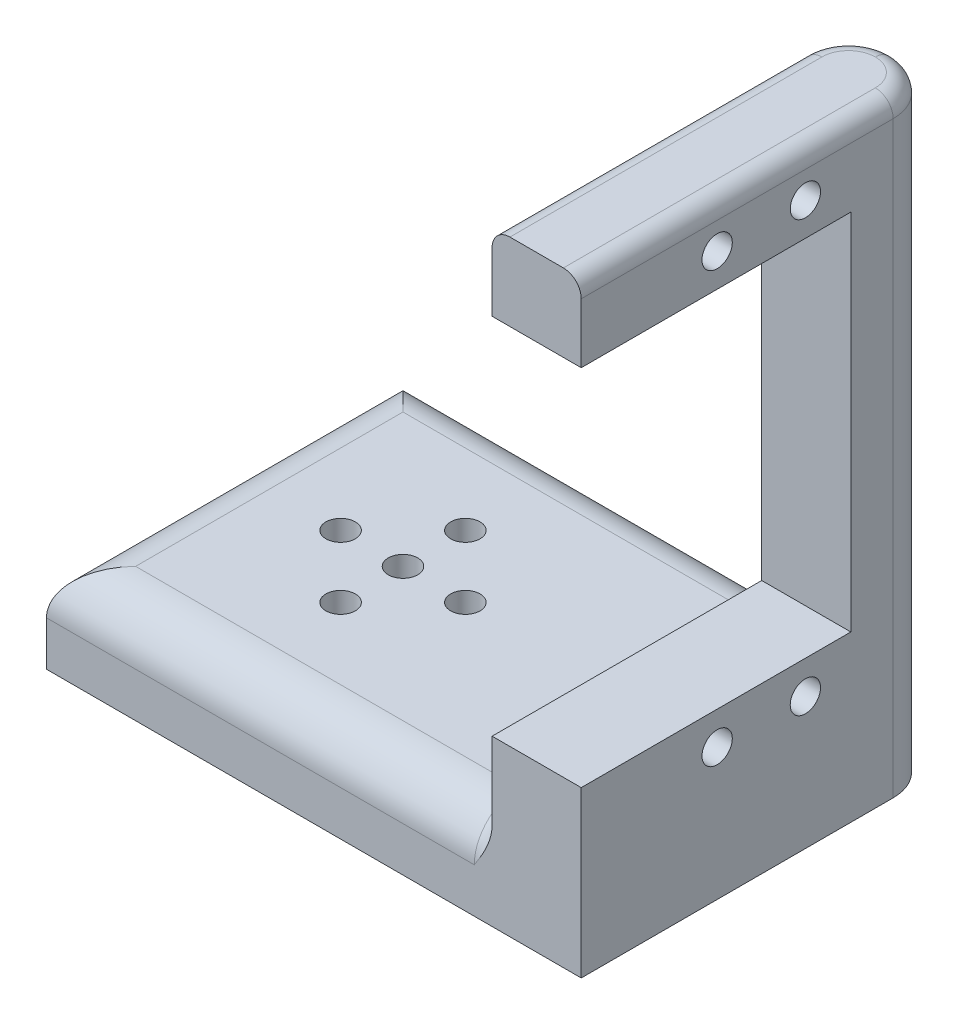
SolidWorks part; units mm, degrees
ref_plane "Front Plane" through (0, 0, 0) normal (0, 0, 1) x (1, 0, 0)
ref_plane "Top Plane" through (0, 0, 0) normal (0, 1, 0) x (1, 0, 0)
ref_plane "Right Plane" through (0, 0, 0) normal (1, 0, 0) x (0, 0, -1)
sketch "Sketch1" plane through (0, 0, 0) normal (0, 0, 1) x (1, 0, 0)
  line L0 (0, 0) -> (0, 68)
  line L1 (0, 68) -> (-10, 68)
  line L2 (-10, 68) -> (-10, 10)
  line L3 (-10, 10) -> (-60, 10)
  line L4 (-60, 10) -> (-60, 0)
  line L5 (-60, 0) -> (0, 0)
  dimension "D1" = 68
  dimension "D2" = 58
  dimension "D3" = 10
  dimension "D4" = 60
extrude "Boss-Extrude2" add sketch "Sketch1" along normal blind 40
sketch "Sketch3" plane through (0, 0, 0) normal (1, 0, 0) x (0, 0, -1)
  line L0 (-9.75, 18.5) -> (-9.75, 59.3)
  line L1 (-9.75, 59.3) -> (-40, 59.3)
  line L2 (-40, 0) -> (-40, 68) construction
  line L3 (-40, 59.3) -> (-40, 18.5)
  line L4 (-40, 18.5) -> (-9.75, 18.5)
  line L5 (-9.75, 38.9) -> (-27.1227, 38.9) construction
  circle A0 centre (-14.85, 63) radius 1.7
  circle A1 centre (-24.75, 63) radius 1.7
  circle A2 centre (-24.75, 14.8) radius 1.7
  circle A3 centre (-14.85, 14.8) radius 1.7
  dimension "D8" = 3.4
  dimension "D9" = 3.4
  dimension "D1" = 30.25
  dimension "D2" = 40.8
  dimension "D3" = 18.5
  dimension "D4" = 3.7
  dimension "D5" = 3.7
  dimension "D6" = 9.9
  dimension "D7" = 5.1
extrude "Cut-Extrude1" cut sketch "Sketch3" against normal up to next
sketch "Sketch4" plane through (0, 0, 0) normal (0, -1, 0) x (1, 0, 0)
  line L0 (0, 40) -> (0, 0) construction
  circle A0 centre (-40, 20) radius 1.65
  circle A1 centre (-40, 20) radius 7 construction
  circle A2 centre (-40, 13) radius 1.65
  circle A3 centre (-33, 20) radius 1.65
  circle A4 centre (-40, 27) radius 1.65
  circle A5 centre (-47, 20) radius 1.65
  dimension "D1" = 3.3
  dimension "D2" = 14
  dimension "D3" = 40
extrude "Cut-Extrude2" cut sketch "Sketch4" against normal up to next
fillet "Fillet1" radius 5 5 edges at (-10, 39, 0) (0, 34, 0) (-35, 10, 40) (-35, 10, 0) (-60, 10, 20)
fillet "Fillet2" radius 2 7 edges at (0, 68, 22.5) (-1.4645, 68, 1.4645) (-8.5355, 68, 1.4645) (-10, 8.5355, 38.5355) (-8.5355, 8.5355, 1.4645) (-10, 68, 22.5) (-10, 10, 20)
equation "\"D1@Sketch3\"=0.975+2.05"
equation "\"D5@Sketch3\"=\"D4@Sketch3\""
equation "\"D9@Sketch3\"=\"D8@Sketch3\""
